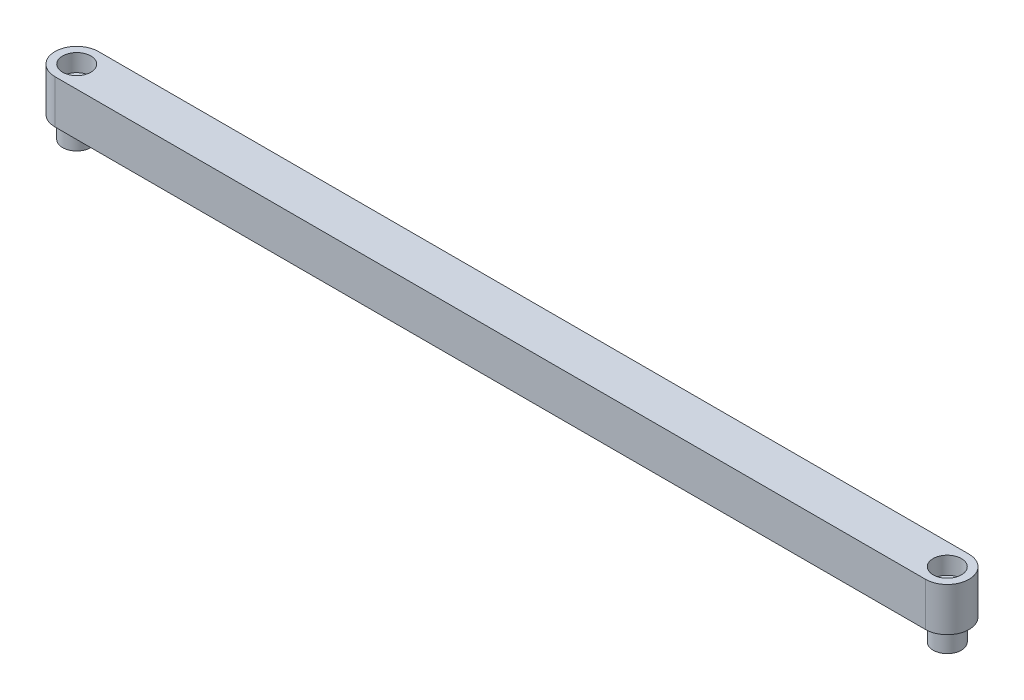
SolidWorks part; units mm, degrees
ref_plane "Front Plane" through (0, 0, 0) normal (0, 0, 1) x (1, 0, 0)
ref_plane "Top Plane" through (0, 0, 0) normal (0, 1, 0) x (1, 0, 0)
ref_plane "Right Plane" through (0, 0, 0) normal (1, 0, 0) x (0, 0, -1)
sketch "Sketch1" plane through (0, 0, 0) normal (0, 1, 0) x (1, 0, 0)
  line L0 (0, 0) -> (600, 0) construction
  line L1 (0, 15) -> (600, 15)
  line L2 (0, -15) -> (600, -15)
  arc A0 (0, 15) -> (0, -15) centre (0, 0) ccw
  arc A1 (600, -15) -> (600, 15) centre (600, 0) ccw
  point P3 (300, 0)
  dimension "D2" = 15
  dimension "D1" = 600
extrude "Boss-Extrude1" add sketch "Sketch1" along normal mid plane 30
sketch "Sketch3" plane through (0, 0, 0) normal (0, 1, 0) x (1, 0, 0)
  circle A0 centre (0, 0) radius 9.75
  circle A1 centre (600, 0) radius 9.75
  dimension "D1" = 19.5
  dimension "D2" = 19.5
extrude "Cut-Extrude2" cut sketch "Sketch3" along normal through all
extrude "Boss-Extrude2" add sketch "Sketch3<3>" along direction (0, -1, 0) on the side against the normal blind 30
sketch "Sketch3<3>" plane through (0, 0, 0) normal (0, 1, 0) x (1, 0, 0) same geometry as "Sketch3"
extrude "Boss-Extrude3" add sketch "Sketch3<4>" along normal blind 3
sketch "Sketch3<4>" plane through (0, 0, 0) normal (0, 1, 0) x (1, 0, 0) same geometry as "Sketch3"
